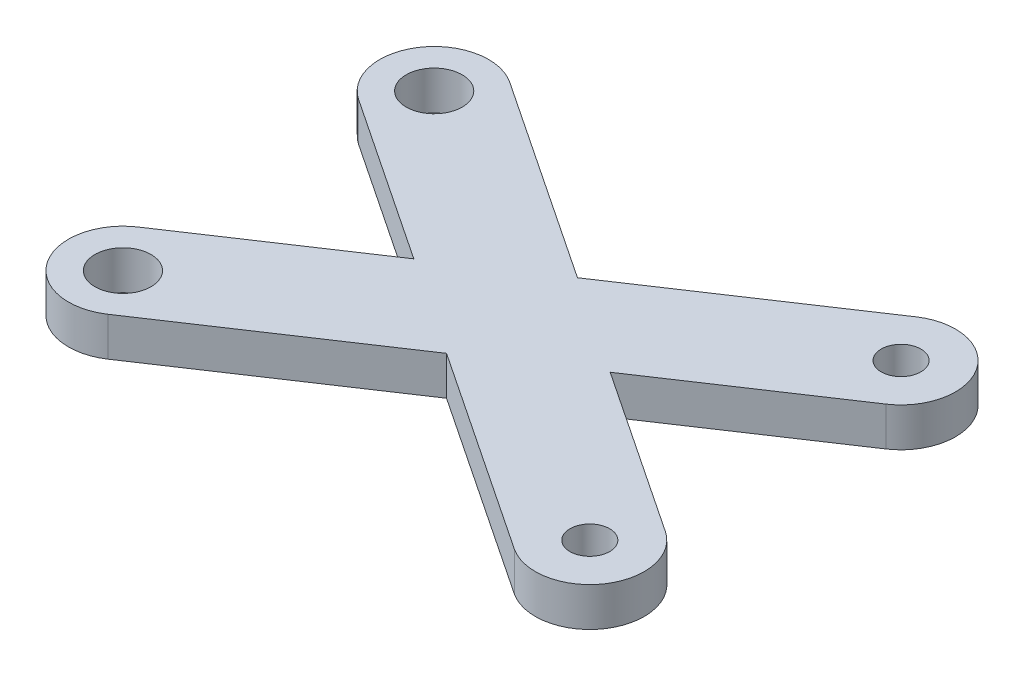
SolidWorks part; units mm, degrees
ref_plane "Front Plane" through (0, 0, 0) normal (0, 0, 1) x (1, 0, 0)
ref_plane "Top Plane" through (0, 0, 0) normal (0, 1, 0) x (1, 0, 0)
ref_plane "Right Plane" through (0, 0, 0) normal (1, 0, 0) x (0, 0, -1)
sketch "Sketch1" plane through (0, 0, 0) normal (0, 1, 0) x (1, 0, 0)
  line L0 (-33.8829, 14.1756) -> (-12.6194, 0)
  line L1 (-30, -20) -> (30, -20) construction
  line L2 (-30, -20) -> (-30, 20) construction
  line L3 (-30, 20) -> (30, 20) construction
  line L4 (30, -20) -> (30, 20) construction
  line L5 (-30, -20) -> (30, 20) construction
  line L6 (-30, 20) -> (30, -20) construction
  line L7 (-26.1171, 25.8244) -> (0, 8.413)
  line L8 (-26.1171, -25.8244) -> (0, -8.413)
  line L9 (-33.8829, -14.1756) -> (-12.6194, 0)
  line L10 (0, -8.413) -> (26.1171, -25.8244)
  line L11 (12.6194, 0) -> (33.8829, 14.1756)
  line L12 (-33.8829, 14.1756) -> (26.1171, -25.8244) construction
  line L13 (12.6194, 0) -> (33.8829, -14.1756)
  line L14 (-26.1171, -25.8244) -> (33.8829, 14.1756) construction
  line L15 (0, 8.413) -> (26.1171, 25.8244)
  line L16 (-26.1171, 25.8244) -> (33.8829, -14.1756) construction
  line L18 (-33.8829, -14.1756) -> (26.1171, 25.8244) construction
  circle A0 centre (30, 20) radius 2.55
  circle A1 centre (30, -20) radius 2.55
  circle A2 centre (-30, -20) radius 3.6
  circle A3 centre (-30, 20) radius 3.6
  arc A8 (-33.8829, 14.1756) -> (-26.1171, 25.8244) centre (-30, 20) cw
  arc A9 (26.1171, 25.8244) -> (33.8829, 14.1756) centre (30, 20) cw
  arc A10 (-26.1171, -25.8244) -> (-33.8829, -14.1756) centre (-30, -20) cw
  arc A11 (33.8829, -14.1756) -> (26.1171, -25.8244) centre (30, -20) cw
  point P0 (0, 0)
  dimension "D3" = 7.2
  dimension "D4" = 7.2
  dimension "D5" = 5.1
  dimension "D6" = 5.1
  dimension "D1" = 60
  dimension "D2" = 40
  dimension "D11" = 7
  dimension "D12" = 7
  dimension "D13" = 7
  dimension "D14" = 7
extrude "Boss-Extrude1" add sketch "Sketch1" along normal blind 5 contours A11 L13 L11 A9 L15 L7 A8 L0 L9 A10 L8 L10 A3 A2 A1 A0 region at (0.6109, 0, 0)
